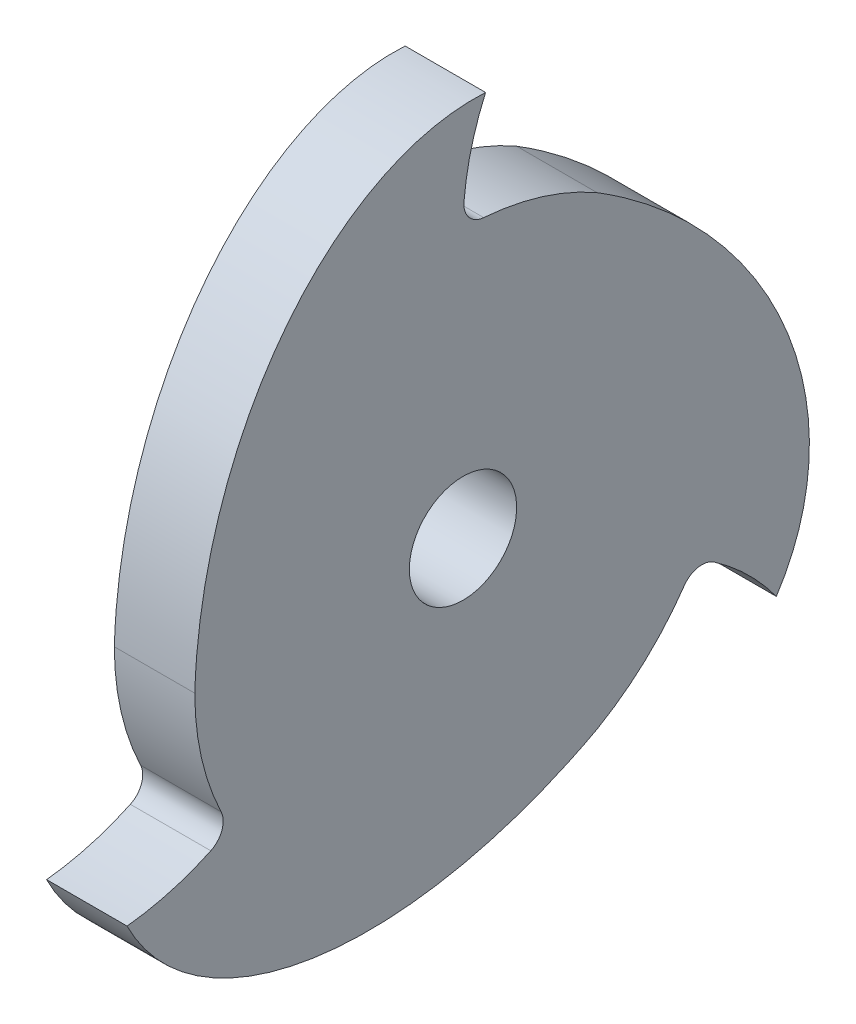
SolidWorks part; units mm, degrees
material "AISI 304"
ref_plane "Front Plane" through (0, 0, 0) normal (0, 0, 1) x (1, 0, 0)
ref_plane "Top Plane" through (0, 0, 0) normal (0, 1, 0) x (1, 0, 0)
ref_plane "Right Plane" through (0, 0, 0) normal (1, 0, 0) x (0, 0, -1)
sketch "Sketch1" plane through (0, 0, 0) normal (1, 0, 0) x (0, 0, -1)
  line L0 (0, 31.75) -> (101.4565, 31.75) construction
  line L1 (0, 0) -> (-38.4948, -22.225) construction
  line L2 (5.2388, 0) -> (-5.2388, 0) construction
  line L3 (0, 0) -> (-44.45, 0) construction
  circle A0 centre (0, 0) radius 31.75
  circle A1 centre (0, 0) radius 44.45
  arc A2 (0, 31.75) -> (2.6746, 44.3695) centre (31.1085, 31.75) cw
  arc A3 (27.4963, -15.875) -> (37.0878, -24.501) centre (11.942, -42.8158) cw
  arc A4 (-27.4963, -15.875) -> (-39.7624, -19.8685) centre (-43.0506, 11.0658) cw
  circle A5 centre (0, 0) radius 6.35
  ellipse E0 centre (0, 0) end of major axis (-2.6746, -44.3695) minor radius 31.7218 (2.6746, 44.3695) -> (-31.75, 0) ccw
  ellipse E1 centre (0, 0) end of major axis (37.0878, -24.501) minor radius 31.7218 (37.0878, -24.501) -> (15.875, 27.4963) ccw
  ellipse E2 centre (0, 0) end of major axis (-39.7624, -19.8685) minor radius 31.7218 (-39.7624, -19.8685) -> (15.875, -27.4963) ccw
  point P35 (0, 0)
  point P37 (0, 0)
  dimension "D1" = 63.5
  dimension "D2" = 88.9
  dimension "D5" = 12.7
  dimension "D3" = 30
  dimension "D4" = 3
extrude "Boss-Extrude3" add sketch "Sketch1" along normal blind 9.525 contours A2 E0 A0 | A0 E2 E1 E0 | A3 E1 A0 | A4 E2 A0 region at (0, 25.7185, -16.9902) region at (0, 32.9164, 12.2363) region at (0, -5.8613, -34.6246) region at (0, -27.0551, 22.3883)
fillet "Fillet3" radius 2.54 3 edges at (4.7625, -15.875, 27.4963) (4.7625, -15.875, -27.4963) (4.7625, 31.75, 0)
